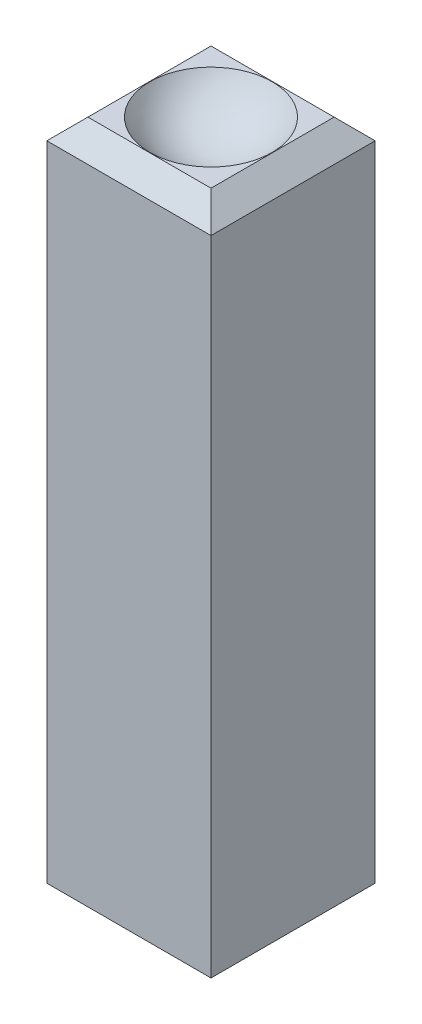
SolidWorks part; units mm, degrees
ref_plane "Front Plane" through (0, 0, 0) normal (0, 0, 1) x (1, 0, 0)
ref_plane "Top Plane" through (0, 0, 0) normal (0, 1, 0) x (1, 0, 0)
ref_plane "Right Plane" through (0, 0, 0) normal (1, 0, 0) x (0, 0, -1)
sketch "Sketch1" plane through (0, 0, 0) normal (0, 1, 0) x (1, 0, 0)
  line L1 (-12, -12) -> (12, -12)
  line L2 (-12, -12) -> (-12, 12)
  line L3 (-12, 12) -> (12, 12)
  line L4 (12, -12) -> (12, 12)
  line L5 (-12, -12) -> (12, 12) construction
  line L6 (-12, 12) -> (12, -12) construction
  line L7 (-10.25, -10.25) -> (10.25, -10.25)
  line L8 (-10.25, -10.25) -> (-10.25, 10.25)
  line L9 (-10.25, 10.25) -> (10.25, 10.25)
  line L10 (10.25, -10.25) -> (10.25, 10.25)
  line L11 (-10.25, -10.25) -> (10.25, 10.25) construction
  line L12 (-10.25, 10.25) -> (10.25, -10.25) construction
  point P0 (0, 0)
  point P6 (0, 0)
  dimension "D1" = 24
  dimension "D2" = 1.75
extrude "Boss-Extrude1" add sketch "Sketch1" along normal mid plane 97 contours L7 L10 L9 L8 | L1 L4 L3 L2 L10 L7 L8 L9 region at (-11.6606, 0, 0) region at (0, 0, 0)
extrude "Cut-Extrude1" cut sketch "Sketch1<4>" along normal blind 40 from surface contours L7 L10 L9 L8 region at (0, 0, 0) starting at face at (0, -48.5, 0)
sketch "Sketch1<4>" plane through (0, 0, 0) normal (0, 1, 0) x (1, 0, 0) same geometry as "Sketch1"
sketch "Sketch3" plane through (0, 0, 0) normal (0, 0, 1) x (1, 0, 0)
  line L0 (-12, -48.5) -> (12, -48.5) construction
  line L3 (-8.9478, 48.5) -> (0, 48.5)
  line L4 (-12, 48.5) -> (12, 48.5) construction
  line L5 (0, 64.8356) -> (0, 36.8669) construction
  line L6 (0, 48.5) -> (0, 43.25)
  circle A0 centre (0, 53.5) radius 7 construction
  arc A1 (-8.9478, 48.5) -> (0, 43.25) centre (0, 53.5) ccw
  dimension "D1" = 14
  dimension "D2" = 109
  dimension "D3" = 3.25
revolve "Cut-Revolve1" cut sketch "Sketch3" angle 360 about L5
chamfer "Chamfer2" distance 3 angle 45 4 edges at (0, 48.5, -12) (12, 48.5, 0) (-12, 48.5, 0) (0, 48.5, 12)
